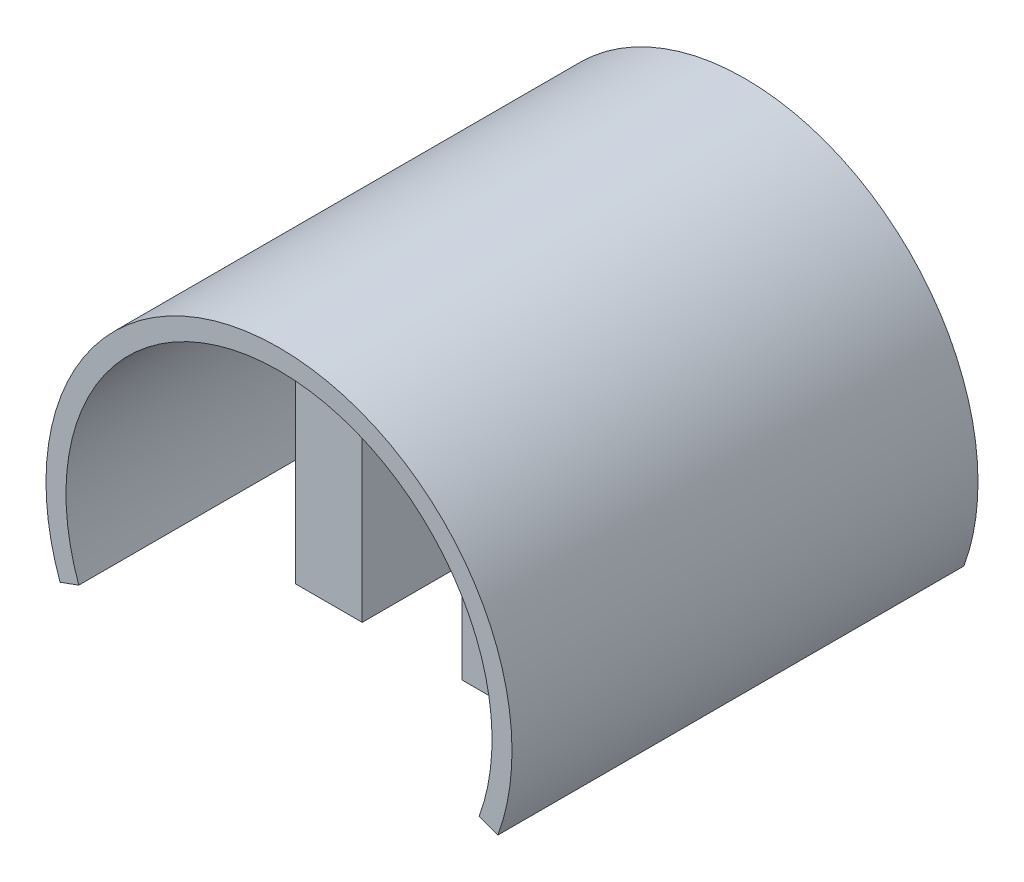
SolidWorks part; units mm, degrees
material "ABS"
ref_plane "Front" through (0, 0, 0) normal (0, 0, 1) x (1, 0, 0)
ref_plane "Top" through (0, 0, 0) normal (0, 1, 0) x (1, 0, 0)
ref_plane "Right" through (0, 0, 0) normal (1, 0, 0) x (0, 0, -1)
sketch "Esquisse1" plane through (0, 0, 0) normal (0, 0, 1) x (1, 0, 0)
  circle A0 centre (0, 0) radius 35
  circle A1 centre (0, 0) radius 32
  dimension "D1" = 70
  dimension "D2" = 3
extrude "Boss.-Extru.1" add sketch "Esquisse1" along normal blind 70
sketch "Esquisse2" plane through (0, 0, 70) normal (0, 0, 1) x (1, 0, 0)
  line L0 (0, 0) -> (0, 35) construction
  line L1 (-7.5, 31.1087) -> (-7.5, -31.1087)
  line L2 (-7.5, 0) -> (-17.5, 0) construction
  line L3 (-17.5, -26.7909) -> (-17.5, 26.7909)
  line L4 (7.5, 0) -> (17.5, 0) construction
  line L5 (17.5, -26.7909) -> (17.5, 26.7909)
  line L6 (7.5, 31.1087) -> (7.5, -31.1087)
  line L7 (0, 0) -> (0, -35) construction
  circle A0 centre (0, 0) radius 35 construction
  circle A1 centre (0, 0) radius 32 construction
  arc A2 (-17.5, 26.7909) -> (-7.5, 31.1087) centre (0, 0) cw
  arc A3 (17.5, 26.7909) -> (7.5, 31.1087) centre (0, 0) ccw
  arc A4 (17.5, -26.7909) -> (7.5, -31.1087) centre (0, 0) cw
  arc A5 (-17.5, -26.7909) -> (-7.5, -31.1087) centre (0, 0) ccw
  dimension "D1" = 10
  dimension "D2" = 35
extrude "Boss.-Extru.2" add sketch "Esquisse2" against normal blind 70
sketch "Esquisse3" plane through (0, 0, 0) normal (0, 1, 0) x (1, 0, 0)
  line L0 (-12.5, 0) -> (-12.5, -70) construction
  line L1 (35, 0) -> (-35, 0) construction
  line L2 (-35, -70) -> (35, -70) construction
  line L3 (-17.5, -25) -> (-7.5, -25) construction
  line L6 (0, -70) -> (0, 0) construction
  line L7 (17.5, -25) -> (7.5, -25) construction
  line L8 (-17.5, 0) -> (-17.5, -70) construction
  line L9 (-7.5, 0) -> (-7.5, -70) construction
  circle A0 centre (-12.5, -10) radius 3.2
  circle A1 centre (-12.5, -40) radius 3.2
  circle A2 centre (12.5, -40) radius 3.2
  circle A3 centre (12.5, -10) radius 3.2
  point P12 (-12.5, -25)
  point P26 (12.5, -25)
  point P40 (-12.5, -25)
  dimension "D1" = 6.4
  dimension "D3" = 10
  dimension "D2" = 15
extrude "Enlèv. mat.-Extru.1" cut sketch "Esquisse3" against normal blind 20 and the other way blind 20
sketch "Esquisse4" [suppressed] plane through (0, 0, 70) normal (0, 0, 1) x (1, 0, 0)
  line L0 (0, -10) -> (0, 0) construction
  line L1 (-50, 50) -> (50, 50)
  line L2 (-50, 50) -> (-50, -10)
  line L3 (-50, -10) -> (50, -10)
  line L4 (50, 50) -> (50, -10)
  dimension "D1" = 15
  dimension "D2" = 60
  dimension "D3" = 100
extrude "Enlèv. mat.-Extru.2" [suppressed] cut sketch "Esquisse4" against normal through all both and the other way through all
sketch "Esquisse5" plane through (0, 0, 70) normal (0, 0, 1) x (1, 0, 0)
  line L0 (0, -6.5) -> (0, 0) construction
  line L1 (-50, -56.5) -> (50, -56.5)
  line L2 (-50, -56.5) -> (-50, -6.5)
  line L3 (-50, -6.5) -> (50, -6.5)
  line L4 (50, -56.5) -> (50, -6.5)
  dimension "D1" = 6.5
  dimension "D2" = 50
  dimension "D3" = 100
extrude "Enlèv. mat.-Extru.3" cut sketch "Esquisse5" against normal through all
sketch "Esquisse7" plane through (0, -6.5, 0) normal (0, -1, 0) x (1, 0, 0)
  line L4 (-7.5, 0) -> (-7.5, 70)
  line L5 (-7.5, 70) -> (-17.5, 70)
  line L6 (-17.5, 70) -> (-17.5, 0)
  line L7 (-17.5, 0) -> (-7.5, 0)
  line L8 (-7.5, 0) -> (-7.5, 70)
  line L9 (-7.5, 70) -> (-17.5, 70)
  line L10 (-17.5, 70) -> (-17.5, 0)
  line L11 (-17.5, 0) -> (-7.5, 0)
  line L12 (17.5, 0) -> (17.5, 70)
  line L13 (17.5, 70) -> (7.5, 70)
  line L14 (7.5, 70) -> (7.5, 0)
  line L15 (7.5, 0) -> (17.5, 0)
  line L16 (17.5, 0) -> (17.5, 70)
  line L17 (17.5, 70) -> (7.5, 70)
  line L18 (7.5, 70) -> (7.5, 0)
  line L19 (7.5, 0) -> (17.5, 0)
  circle A0 centre (-12.5, 40) radius 3.2 construction
  circle A1 centre (-12.5, 40) radius 3.2
  circle A2 centre (-12.5, 10) radius 3.2 construction
  circle A3 centre (-12.5, 10) radius 3.2
  circle A4 centre (12.5, 40) radius 3.2 construction
  circle A5 centre (12.5, 40) radius 3.2
  circle A6 centre (12.5, 10) radius 3.2 construction
  circle A7 centre (12.5, 10) radius 3.2
  dimension "D1" = 0
  dimension "D2" = 0
extrude "Boss.-Extru.3" add sketch "Esquisse7" along normal blind 8
sketch "Esquisse8" plane through (0, 0, 70) normal (0, 0, 1) x (1, 0, 0)
  line L0 (32.8892, -11.9707) -> (30.0702, -10.9446)
  line L1 (30.0702, -10.9446) -> (0, 0) construction
  line L2 (34.3911, -6.5) -> (31.3329, -6.5) construction
  line L3 (0, 0) -> (0, 9.4102) construction
  line L4 (-32.8892, -11.9707) -> (-30.0702, -10.9446)
  line L5 (-34.3911, -6.5) -> (-31.3329, -6.5)
  line L6 (34.3911, -6.5) -> (31.3329, -6.5)
  arc A0 (31.3329, -6.5) -> (30.0702, -10.9446) centre (0, 0) cw
  arc A1 (34.3911, -6.5) -> (32.8892, -11.9707) centre (0, 0) cw
  arc A2 (-34.3911, -6.5) -> (-32.8892, -11.9707) centre (0, 0) ccw
  arc A3 (-31.3329, -6.5) -> (-30.0702, -10.9446) centre (0, 0) ccw
  dimension "D1" = 20
extrude "Boss.-Extru.5" add sketch "Esquisse8" against normal up to vertex (70 mm away) up to point (34.3911, -6.5, 0)
sketch "Esquisse10" plane through (0, 0, 70) normal (0, 0, 1) x (1, 0, 0)
  circle A0 centre (0, 0) radius 32
  dimension "D1" = 64
extrude "Enlèv. mat.-Extru.4" cut sketch "Esquisse10" against normal blind 20
fillet "Congé1" [suppressed] radius 2
fillet "Congé2" radius 2 4 edges at (-17.5, 26.7909, 25) (-7.5, 31.1087, 25) (17.5, 26.7909, 25) (7.5, 31.1087, 25)
sketch "Esquisse11" plane through (0, -14.5, 0) normal (0, -1, 0) x (1, 0, 0)
  circle A0 centre (12.5, 10) radius 3.2
  circle A1 centre (12.5, 40) radius 3.2
  circle A2 centre (-12.5, 40) radius 3.2
  circle A3 centre (-12.5, 10) radius 3.2
  circle A4 centre (12.5, 10) radius 3.2 construction
extrude "Boss.-Extru.6" add sketch "Esquisse11" against normal up to surface (33 mm away) from offset 1.5 up to face at (12.5, 20, 6.8) offset against normal yes
